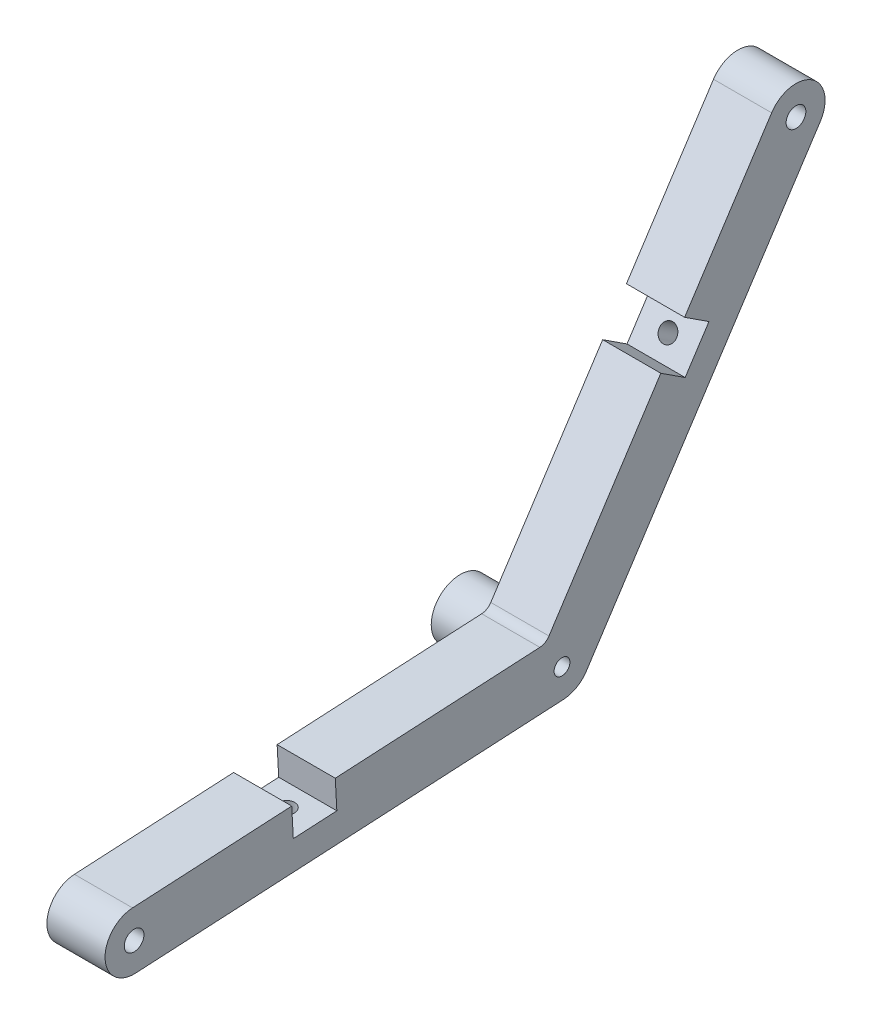
SolidWorks part; units mm, degrees
material "Custom Plastic"
ref_plane "Front Plane" through (0, 0, 0) normal (0, 0, 1) x (1, 0, 0)
ref_plane "Top Plane" through (0, 0, 0) normal (0, 1, 0) x (1, 0, 0)
ref_plane "Right Plane" through (0, 0, 0) normal (1, 0, 0) x (0, 0, -1)
sketch "Sketch1" plane through (0, 0, 0) normal (1, 0, 0) x (0, 0, -1)
  line L0 (60.5924, 72.9491) -> (13.8564, -8) construction
  line L1 (0, -16) -> (-93.472, -16) construction
  line L2 (-93.8143, 1.2945) -> (-3.5605, 6.167)
  line L3 (-93.1297, -11.387) -> (0.3423, -6.3408)
  line L4 (-3.5605, 6.167) -> (45.7861, 81.8928)
  line L5 (56.4263, 74.9592) -> (5.3201, -3.4668)
  line L6 (-3.5605, 6.167) -> (-0.3423, 6.3408) construction
  line L7 (-3.5605, 6.167) -> (-5.3201, 3.4668) construction
  circle A0 centre (0, 0) radius 16 construction
  circle A1 centre (51.1062, 78.426) radius 10.9537 construction
  circle A2 centre (-93.472, -5.0463) radius 10.9538 construction
  arc A3 (-93.8143, 1.2945) -> (-93.1297, -11.387) centre (-93.472, -5.0463) ccw
  arc A4 (0.3423, -6.3408) -> (5.3201, -3.4668) centre (0, 0) ccw
  arc A5 (56.4263, 74.9592) -> (45.7861, 81.8928) centre (51.1062, 78.426) ccw
  dimension "D3" = 21.9075
  dimension "D4" = 32
  dimension "D5" = 12.7
  dimension "D1" = 120
  dimension "D2" = 93.472
extrude "Boss-Extrude1" add sketch "Sketch1" along normal blind 12.7
sketch "Sketch2" plane through (12.7, 0, 0) normal (1, 0, 0) x (0, 0, -1)
  line L0 (-54.2867, 3.4285) -> (-53.602, -9.253) construction
  line L1 (-3.5605, 6.167) -> (-93.8143, 1.2945) construction
  line L2 (-93.1297, -11.387) -> (0.3423, -6.3408) construction
  line L3 (24.1742, 48.7279) -> (34.8144, 41.7942) construction
  line L4 (45.7861, 81.8928) -> (-3.5605, 6.167) construction
  line L5 (5.3201, -3.4668) -> (56.4263, 74.9592) construction
  line L6 (-59.0422, 3.1717) -> (-58.6999, -3.169)
  line L7 (-58.6999, -3.169) -> (-49.1888, -2.6555)
  line L8 (-49.1888, -2.6555) -> (-49.5311, 3.6852)
  line L9 (21.574, 44.7378) -> (26.8942, 41.271)
  line L10 (26.8942, 41.271) -> (32.0944, 49.2511)
  line L11 (32.0944, 49.2511) -> (26.7743, 52.718)
  line L12 (-59.0422, 3.1717) -> (-49.5311, 3.6852)
  line L13 (26.7743, 52.718) -> (21.574, 44.7378)
  point P15 (-53.9443, -2.9123)
  point P21 (29.4943, 45.261)
  dimension "D1" = 9.525
  dimension "D2" = 9.525
  dimension "D3" = 50.8
  dimension "D4" = 50.8
extrude "Cut-Extrude1" cut sketch "Sketch2" against normal through all
sketch "Sketch6" plane through (0, 0, 0) normal (-1, 0, 0) x (0, 0, 1)
  circle A0 centre (0, 0) radius 6.35
  arc A1 (-5.3201, -3.4668) -> (-0.3423, -6.3408) centre (0, 0) ccw construction
extrude "Boss-Extrude2" add sketch "Sketch6" along normal blind 9.525
hole_wizard "Axel Holes" positions "3DSketch1" profile "Sketch3" hole size "#4" standard "ANSI Inch" end condition through all
sketch3d "3DSketch1"
  arc A0 (12.7, -6.3408, -0.3423) -> (12.7, -3.4668, -5.3201) centre (12.7, 0, 0) ccw construction
  point P4 (12.7, 0, 0)
  point P15 (19.05, 0, 0)
sketch "Sketch3" plane through (12.7, 0, 0) normal (0, 1, 0) x (0, 0, -1)
  line L0 (0, 0) -> (0, 22.225)
  line L1 (0, 22.225) -> (1.7272, 22.225)
  line L2 (1.7272, 22.225) -> (1.7272, 0)
  line L5 (1.7272, 0) -> (0, 0)
  line L11 (0, -6.35) -> (0, 107.95) construction
  dimension "Thru Hole Dia." = 3.4544
  dimension "Thru Hole Depth" = 22.225
hole_wizard "Long Axel Holes" positions "3DSketch5" profile "Sketch7" hole size "#6" standard "ANSI Inch" end condition through all
sketch3d "3DSketch5"
  line L0 (12.7, -5.0463, 93.472) -> (0, -5.0463, 93.472) construction
  line L1 (12.7, 78.426, -51.1062) -> (0, 78.426, -51.1062) construction
  point P0 (12.7, -5.0463, 93.472)
  point P4 (12.7, 78.426, -51.1062)
sketch "Sketch7" plane through (12.7, -5.0463, 93.472) normal (0, 1, 0) x (0, 0, -1)
  line L0 (0, 0) -> (0, 22.225)
  line L1 (0, 22.225) -> (2.1526, 22.225)
  line L2 (2.1526, 22.225) -> (2.1526, 0)
  line L5 (2.1526, 0) -> (0, 0)
  line L11 (0, -6.35) -> (0, 107.95) construction
  dimension "Thru Hole Dia." = 4.3053
  dimension "Thru Hole Depth" = 22.225
hole_wizard "Mounting Holes" positions "3DSketch4" profile "Sketch5" hole size "#6" standard "ANSI Inch" end condition through all
sketch3d "3DSketch4"
  line L0 (0, -2.6555, 49.1888) -> (12.7, -3.169, 58.6999) construction
  line L2 (0, 41.271, -26.8942) -> (12.7, 49.2511, -32.0944) construction
  point P0 (6.35, -2.9123, 53.9443)
  point P2 (6.35, 45.261, -29.4943)
  point P11 (6.35, -2.9123, 53.9443)
  point P18 (6.35, 45.261, -29.4943)
sketch "Sketch5" plane through (6.35, -2.9123, 53.9443) normal (1, 0, 0) x (0, -0.0539, 0.9985)
  line L0 (0, 0) -> (0, 14.477)
  line L1 (0, 14.477) -> (1.8986, 14.477)
  line L2 (1.8986, 14.477) -> (1.8986, 0)
  line L5 (1.8986, 0) -> (0, 0)
  line L11 (0, -6.35) -> (0, 107.95) construction
  dimension "Thru Hole Dia." = 3.7973
  dimension "Thru Hole Depth" = 14.477
fillet "Fillet1" radius 2.54 1 edges at (6.35, 6.167, 3.5605)
sketch "Sketch9" plane through (0, 0, 0) normal (-1, 0, 0) x (0, 0, 1)
  line L0 (16.3466, -3.6631) -> (36.5837, -5.0545) construction
  text T0 "<b>Size 1</b>"
extrude "Cut-Extrude2" cut sketch "Sketch9" against normal blind 0.508
sketch "Sketch10" [suppressed] plane through (0, 0, 0) normal (-1, 0, 0) x (0, 0, 1)
  line L0 (12.6638, -3.6473) -> (36.0763, -4.9287) construction
  text T0 "<b>Size 2</b>"
extrude "Cut-Extrude3" [suppressed] cut sketch "Sketch10" against normal blind 0.508
sketch "Sketch11" [suppressed] plane through (0, 0, 0) normal (-1, 0, 0) x (0, 0, 1)
  line L0 (11.4545, -3.3767) -> (31.8024, -4.4996) construction
  text T0 "<b>Size 3</b>"
extrude "Cut-Extrude4" [suppressed] cut sketch "Sketch11" against normal blind 0.508
sketch "Sketch12" [suppressed] plane through (0, 0, 0) normal (-1, 0, 0) x (0, 0, 1)
  line L0 (11.8492, -2.9701) -> (32.3805, -4.1094) construction
  text T0 "<b>Size 4</b>"
extrude "Cut-Extrude5" [suppressed] cut sketch "Sketch12" against normal blind 0.508
equation "\"D2@Sketch2\"=\"D1@Sketch2\""
equation "\"D4@Sketch2\"=\"D3@Sketch2\""
